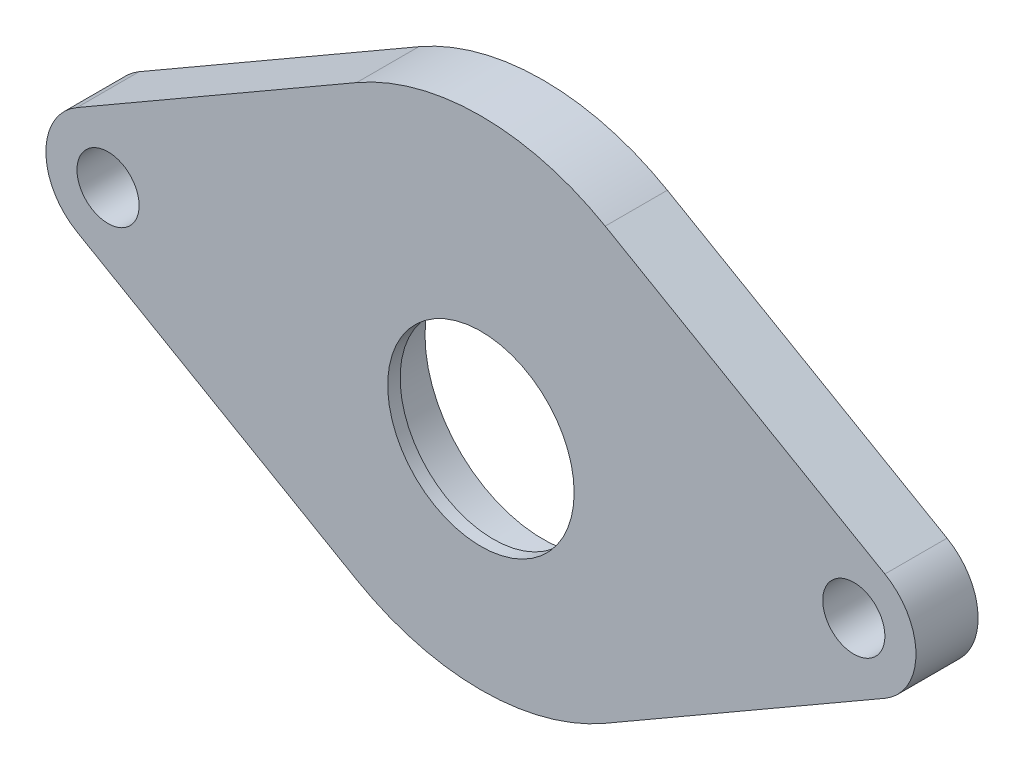
SolidWorks part; units mm, degrees
ref_plane "Front Plane" through (0, 0, 0) normal (0, 0, 1) x (1, 0, 0)
ref_plane "Top Plane" through (0, 0, 0) normal (0, 1, 0) x (1, 0, 0)
ref_plane "Right Plane" through (0, 0, 0) normal (1, 0, 0) x (0, 0, -1)
sketch "Sketch1" plane through (0, 0, 0) normal (0, 0, 1) x (1, 0, 0)
  line L0 (-20, 99.641) -> (-65, 73.6603) construction
  line L1 (-65, 56.3397) -> (-20, 30.359) construction
  line L2 (20, 30.359) -> (65, 56.3397) construction
  line L3 (65, 73.6603) -> (20, 99.641) construction
  line L4 (-20, 99.641) -> (-65, 73.6603)
  line L5 (-65, 56.3397) -> (-20, 30.359)
  line L6 (20, 30.359) -> (65, 56.3397)
  line L7 (65, 73.6603) -> (20, 99.641)
  circle A0 centre (0, 60) radius 15 construction
  circle A1 centre (-60, 65) radius 5 construction
  arc A2 (-65, 73.6603) -> (-65, 56.3397) centre (-60, 65) ccw construction
  arc A3 (-20, 30.359) -> (20, 30.359) centre (0, 65) ccw construction
  circle A4 centre (60, 65) radius 5 construction
  arc A5 (65, 56.3397) -> (65, 73.6603) centre (60, 65) ccw construction
  arc A6 (20, 99.641) -> (-20, 99.641) centre (0, 65) ccw construction
  circle A7 centre (0, 60) radius 15
  circle A8 centre (-60, 65) radius 5
  arc A9 (-65, 73.6603) -> (-65, 56.3397) centre (-60, 65) ccw
  arc A10 (-20, 30.359) -> (20, 30.359) centre (0, 65) ccw
  circle A11 centre (60, 65) radius 5
  arc A12 (65, 56.3397) -> (65, 73.6603) centre (60, 65) ccw
  arc A13 (20, 99.641) -> (-20, 99.641) centre (0, 65) ccw
  circle A14 centre (0, 60) radius 19
  dimension "D1" = 4
extrude "Boss-Extrude1" add sketch "Sketch1" along normal blind 10 contours L6 A12 L7 A13 L4 A9 L5 A10
extrude "Cut-Extrude1" cut sketch "Sketch1<3>" along normal blind 10 contours A8 | A11 | A7
sketch "Sketch1<3>" plane through (0, 0, 0) normal (0, 0, 1) x (1, 0, 0) same geometry as "Sketch1"
extrude "Cut-Extrude2" cut sketch "Sketch1<4>" along normal blind 8 contours A14
sketch "Sketch1<4>" plane through (0, 0, 0) normal (0, 0, 1) x (1, 0, 0) same geometry as "Sketch1"
